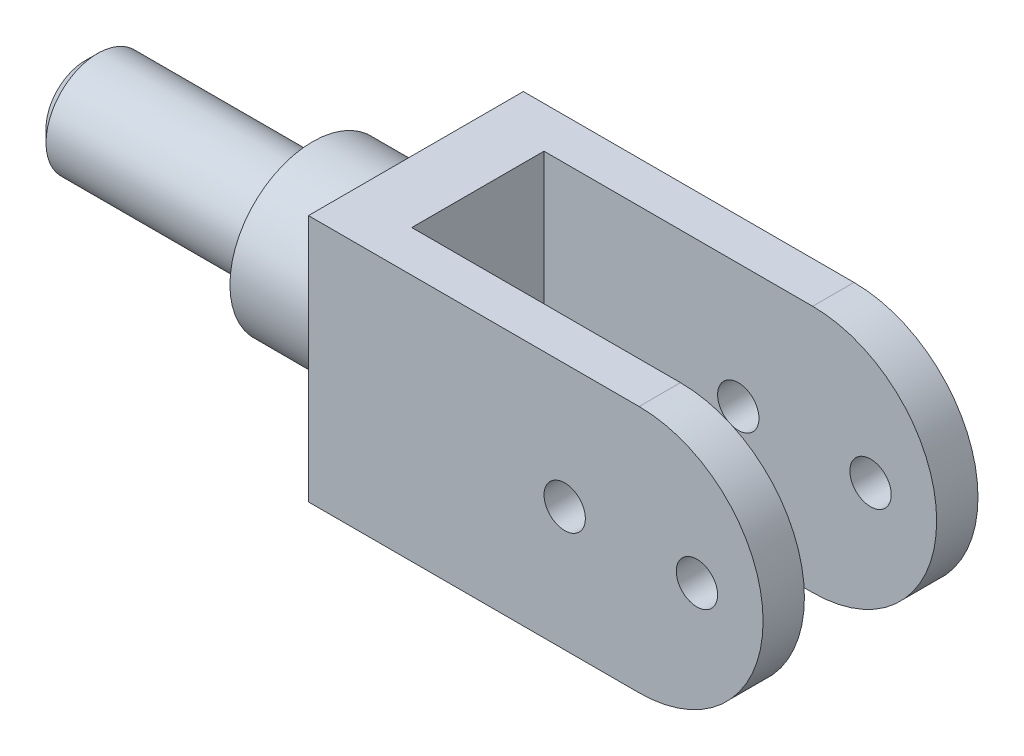
SolidWorks part; units mm, degrees
ref_plane "Front Plane" through (0, 0, 0) normal (0, 0, 1) x (1, 0, 0)
ref_plane "Top Plane" through (0, 0, 0) normal (0, 1, 0) x (1, 0, 0)
ref_plane "Right Plane" through (0, 0, 0) normal (1, 0, 0) x (0, 0, -1)
sketch "Sketch1" plane through (0, 0, 0) normal (0, 1, 0) x (1, 0, 0)
  line L0 (110, 10) -> (110, 0)
  line L9 (0, 52) -> (110, 52)
  line L11 (0, 0) -> (110, 0)
  line L12 (110, 52) -> (110, 42)
  line L13 (110, 42) -> (15, 42)
  line L15 (110, 10) -> (15, 10)
  line L16 (15, 42) -> (15, 10)
  line L17 (0, 52) -> (0, 0)
  dimension "D1" = 110
  dimension "D2" = 15
  dimension "D6" = 52
  dimension "D8" = 10
extrude "Boss-Extrude2" add sketch "Sketch1" along normal blind 60
sketch "Sketch2" plane through (0, 0, 0) normal (0, 0, 1) x (1, 0, 0)
  line L0 (110, 60) -> (110, 0) construction
  line L1 (0, 0) -> (110, 0) construction
  line L2 (80, 60) -> (110, 60)
  line L3 (110, 60) -> (110, 0)
  line L4 (110, 0) -> (80, 0)
  arc A1 (80, 0) -> (80, 60) centre (80, 30) ccw
  line M5 (0, 0) -> (110, 0)
  line M6 (110, 0) -> (110, 60)
  line M7 (110, 60) -> (0, 60)
  dimension "D2" = 60
  dimension "D1" = 30
  dimension "D3" = 30
  dimension "D4" = 30
extrude "Cut-Extrude1" cut sketch "Sketch2" against normal through all contours A1 L3 M7 | A1 M5 M6 region at (103.299, 6.701, 0) region at (103.299, 53.299, 0)
sketch "Sketch3" plane through (0, 0, 0) normal (-1, 0, 0) x (0, 0, 1)
  line L1 (0, 60) -> (0, 0) construction
  line L3 (-52, 0) -> (0, 0) construction
  circle A0 centre (-26, 30) radius 12.5
  circle A1 centre (-26, 30) radius 20
  dimension "D3" = 40
  dimension "D4" = 25
  dimension "D1" = 26
  dimension "D2" = 30
extrude "Boss-Extrude3" add sketch "Sketch3" along normal blind 80 contours A0 region at (0, 30, -26)
extrude "Boss-Extrude4" add sketch "Sketch3<3>" along normal blind 25
sketch "Sketch3<3>" plane through (0, 0, 0) normal (-1, 0, 0) x (0, 0, 1) same geometry as "Sketch3"
fillet "Fillet2" radius 6 1 edges at (0, 30, -46)
chamfer "Chamfer1" distance 3 angle 45 1 edges at (-80, 30, -13.5)
sketch "Sketch4" plane through (0, 0, 0) normal (0, 0, 1) x (1, 0, 0)
  line L0 (-80, 39.5) -> (-80, 20.5) construction
  circle A0 centre (62, 30) radius 5
  circle A1 centre (94, 30) radius 5
  point P4 (0, 0)
  dimension "D3" = 10
  dimension "D1" = 142
  dimension "D2" = 174
extrude "Cut-Extrude2" cut sketch "Sketch4" against normal through all both and the other way through all
